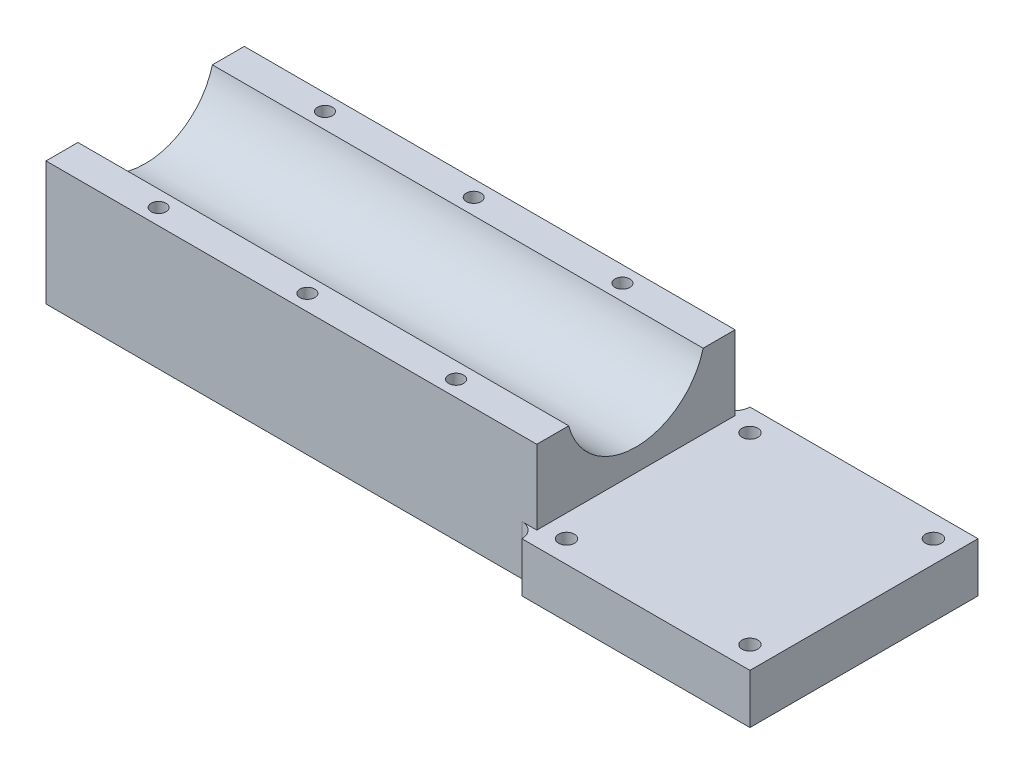
SolidWorks part; units mm, degrees
ref_plane "前视基准面" through (0, 0, 0) normal (0, 0, 1) x (1, 0, 0)
ref_plane "上视基准面" through (0, 0, 0) normal (0, 1, 0) x (1, 0, 0)
ref_plane "右视基准面" through (0, 0, 0) normal (1, 0, 0) x (0, 0, -1)
other "Configuration Table"
sketch "草图1" plane through (0, 0, 0) normal (1, 0, 0) x (0, 0, -1)
  line L1 (0, 0) -> (40, 0)
  line L2 (0, 0) -> (0, -25)
  line L3 (0, -25) -> (40, -25)
  line L4 (40, 0) -> (40, -25)
  dimension "D1" = 40
  dimension "D2" = 25
extrude "凸台-拉伸1" add sketch "草图1" along normal blind 99
sketch "草图2" plane through (0, 0, 0) normal (-1, 0, 0) x (0, 0, 1)
  line L0 (-20, -30.25) -> (-20, -50030.25) construction
  line L1 (0, -25) -> (-40, -25) construction
  circle A0 centre (-20, 3.5) radius 14
  point P4 (-20, -25)
  dimension "D2" = 28
  dimension "D1" = 28.5
extrude "切除-拉伸1" cut sketch "草图2" against normal through all
sketch "草图3" plane through (0, -25, 0) normal (0, -1, 0) x (-1, 0, 0)
  line L0 (-99, 0) -> (-99, 40) construction
  line L1 (-99, -3) -> (-145, -3)
  line L2 (-99, -3) -> (-99, 43)
  line L3 (-99, 43) -> (-145, 43)
  line L4 (-145, -3) -> (-145, 43)
  line L5 (-99, 20) -> (0, 20) construction
  line L6 (0, 0) -> (0, 40) construction
  dimension "D1" = 46
  dimension "D2" = 46
extrude "凸台-拉伸2" add sketch "草图3" against normal blind 10
sketch "草图4" plane through (0, -25, 0) normal (0, -1, 0) x (-1, 0, 0)
  line L0 (-103.5, 1.5) -> (-140.5, 1.5) construction
  line L1 (-140.5, 1.5) -> (-140.5, 38.5) construction
  line L2 (-140.5, 38.5) -> (-103.5, 38.5) construction
  line L3 (-103.5, 38.5) -> (-103.5, 1.5) construction
  line L4 (-122, -3) -> (-122, 1.5) construction
  line L5 (-145, -3) -> (-99, -3) construction
  line L6 (-140.5, 20) -> (-145, 20) construction
  line L7 (-145, 43) -> (-145, -3) construction
  circle A0 centre (-103.5, 1.5) radius 1.6
  circle A1 centre (-140.5, 1.5) radius 1.6
  circle A2 centre (-103.5, 38.5) radius 1.6
  circle A3 centre (-140.5, 38.5) radius 1.6
  dimension "D2" = 3.2
  dimension "D1" = 37
extrude "切除-拉伸2" cut sketch "草图4" against normal blind 10
sketch "草图5" plane through (0, -25, 0) normal (0, -1, 0) x (-1, 0, 0)
  circle A0 centre (-103.5, 1.5) radius 3
  circle A1 centre (-103.5, 38.5) radius 3
  circle A2 centre (-140.5, 38.5) radius 3
  circle A3 centre (-140.5, 1.5) radius 3
  dimension "D1" = 6
extrude "切除-拉伸3" cut sketch "草图5" against normal blind 4
fillet "圆角1" radius 3 2 edges at (99, -20, -40) (99, -20, 0)
sketch "草图6" plane through (0, 0, 0) normal (0, 1, 0) x (1, 0, 0)
  line L0 (0, 36.7777) -> (50000, 36.7777) construction
  line L1 (0, 40) -> (0, 33.5554) construction
  line L2 (0, 3.2223) -> (50000, 3.2223) construction
  line L3 (0, 6.4446) -> (0, 0) construction
  line L4 (49.5, 40) -> (49.5, 36.7777) construction
  line L5 (99, 40) -> (0, 40) construction
  line L6 (49.5, 36.7777) -> (49.5, 3.2223) construction
  line L7 (19.5, 36.7777) -> (19.5, 3.2223) construction
  line L8 (79.5, 36.7777) -> (79.5, 3.2223) construction
  circle A0 centre (49.5, 36.7777) radius 1.5
  circle A1 centre (49.5, 3.2223) radius 1.5
  circle A2 centre (19.5, 36.7777) radius 1.5
  circle A3 centre (19.5, 3.2223) radius 1.5
  circle A4 centre (79.5, 36.7777) radius 1.5
  circle A5 centre (79.5, 3.2223) radius 1.5
  point P4 (0, 36.7777)
  point P9 (0, 3.2223)
  dimension "D1" = 3
  dimension "D2" = 30
  dimension "D3" = 30
  dimension "D4" = 33.5554
extrude "切除-拉伸4" cut sketch "草图6" against normal blind 10
